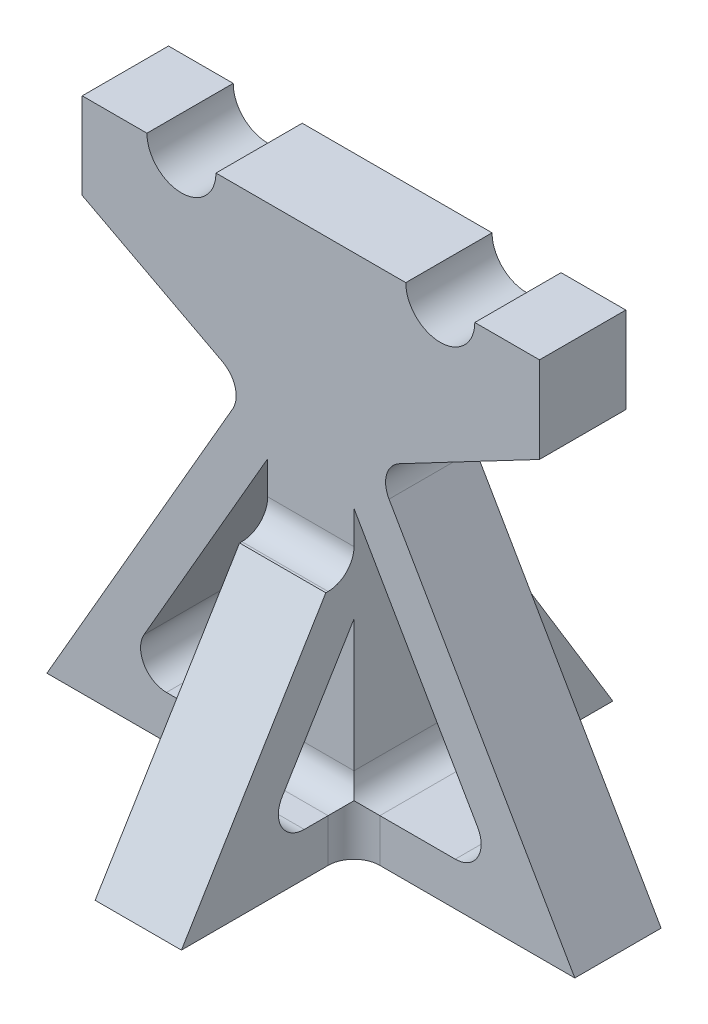
SolidWorks part; units mm, degrees
ref_plane "Front Plane" through (0, 0, 0) normal (0, 0, 1) x (1, 0, 0)
ref_plane "Top Plane" through (0, 0, 0) normal (0, 1, 0) x (1, 0, 0)
ref_plane "Right Plane" through (0, 0, 0) normal (1, 0, 0) x (0, 0, -1)
sketch "Sketch1" plane through (0, 0, 0) normal (0, 0, 1) x (1, 0, 0)
  line L0 (27.94, 152.4) -> (-27.94, 152.4)
  line L1 (-48.26, 152.4) -> (-67.31, 152.4)
  line L2 (-67.31, 152.4) -> (-67.31, 127)
  line L3 (-67.31, 127) -> (-19.05, 101.6)
  line L5 (19.05, 101.6) -> (67.31, 127)
  line L6 (67.31, 127) -> (67.31, 152.4)
  line L7 (67.31, 152.4) -> (48.26, 152.4)
  line L8 (0, 101.6) -> (0, 152.4) construction
  line L9 (-19.05, 101.6) -> (-77.7088, 0)
  line L10 (-77.7088, 0) -> (77.7088, 0)
  line L11 (19.05, 101.6) -> (77.7088, 0)
  line L12 (-55.7117, 12.7) -> (-12.7, 12.7)
  line L13 (-12.7, 87.1985) -> (-55.7117, 12.7)
  line L14 (-12.7, 87.1985) -> (-12.7, 12.7)
  line L15 (12.7, 87.1985) -> (12.7, 12.7)
  line L16 (12.7, 12.7) -> (55.7117, 12.7)
  line L17 (55.7117, 12.7) -> (12.7, 87.1985)
  line L18 (12.7, 12.7) -> (-12.7, 12.7) construction
  line L19 (-19.05, 101.6) -> (19.05, 101.6) construction
  arc A0 (48.26, 152.4) -> (27.94, 152.4) centre (38.1, 152.4) cw
  arc A1 (-27.94, 152.4) -> (-48.26, 152.4) centre (-38.1, 152.4) cw
  point P24 (0, 12.7)
  point P25 (0, 0)
  dimension "D1" = 76.2
  dimension "D2" = 10.16
  dimension "D3" = 25.4
  dimension "D4" = 38.1
  dimension "D5" = 50.8
  dimension "D6" = 152.4
  dimension "D7" = 25.4
  dimension "D8" = 12.7
  dimension "D9" = 60
  dimension "D10" = 12.7
  dimension "D11" = 19.05
extrude "Boss-Extrude1" add sketch "Sketch1" along normal blind 12.7 and the other way blind 12.7
sketch "Sketch2" plane through (0, 0, 0) normal (1, 0, 0) x (0, 0, -1)
  line L0 (20.9925, 69.85) -> (63.5, 0)
  line L1 (63.5, 0) -> (-63.5, 0)
  line L2 (-63.5, 0) -> (-20.9925, 69.85)
  line L3 (-20.9925, 69.85) -> (20.9925, 69.85)
  line L4 (12.7, 59.0469) -> (40.9046, 12.7)
  line L5 (40.9046, 12.7) -> (12.7, 12.7)
  line L6 (12.7, 12.7) -> (12.7, 59.0469)
  line L7 (-12.7, 59.0469) -> (-12.7, 12.7)
  line L8 (-12.7, 12.7) -> (-40.9046, 12.7)
  line L9 (-40.9046, 12.7) -> (-12.7, 59.0469)
  line L10 (-12.7, 101.6) -> (-12.7, 0) construction
  line L11 (12.7, 101.6) -> (12.7, 0) construction
  point P17 (-59.9985, 0)
  point P19 (-12.7, 57.6598)
  point P20 (-12.7, 59.0469)
  point P21 (18.339, 69.85)
  dimension "D1" = 12.7
  dimension "D2" = 12.7
  dimension "D3" = 127
  dimension "D4" = 31.75
  dimension "D5" = 10.8031
extrude "Boss-Extrude2" add sketch "Sketch2" along normal blind 12.7 and the other way blind 12.7
fillet "Fillet1" radius 7.62 2 edges at (0, 69.85, -12.7) (0, 69.85, 12.7)
fillet "Fillet2" radius 7.62 10 edges at (-12.7, 6.35, -12.7) (12.7, 6.35, -12.7) (12.7, 6.35, 12.7) (-12.7, 6.35, 12.7) (-19.05, 101.6, 0) (19.05, 101.6, 0) (55.7117, 12.7, 0) (0, 12.7, -40.9046) (0, 12.7, 40.9046) (-55.7117, 12.7, 0)
fillet "Fillet3" radius 7.62 4 edges at (12.7, 12.7, 0) (0, 12.7, -12.7) (0, 12.7, 12.7) (-12.7, 12.7, 0)
